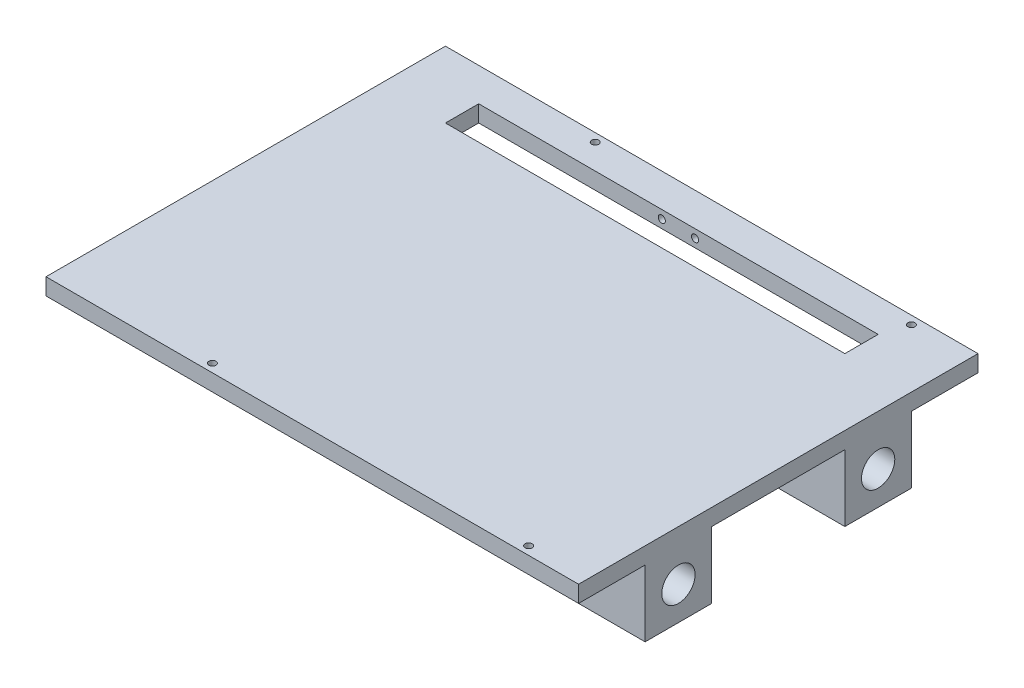
SolidWorks part; units mm, degrees
ref_plane "Front Plane" through (0, 0, 0) normal (0, 0, 1) x (1, 0, 0)
ref_plane "Top Plane" through (0, 0, 0) normal (0, 1, 0) x (1, 0, 0)
ref_plane "Right Plane" through (0, 0, 0) normal (1, 0, 0) x (0, 0, -1)
sketch "Sketch2" plane through (0, 0, 0) normal (0, 1, 0) x (1, 0, 0)
  line L1 (-101.6, -76.2) -> (101.6, -76.2)
  line L2 (-101.6, -76.2) -> (-101.6, 76.2)
  line L3 (-101.6, 76.2) -> (101.6, 76.2)
  line L4 (101.6, -76.2) -> (101.6, 76.2)
  line L5 (-101.6, -76.2) -> (101.6, 76.2) construction
  line L6 (-101.6, 76.2) -> (101.6, -76.2) construction
  point P0 (0, 0)
  dimension "D1" = 203.2
  dimension "D2" = 152.4
extrude "Boss-Extrude1" add sketch "Sketch2" along normal blind 6.35
sketch "Sketch3" plane through (0, 6.35, 0) normal (0, 1, 0) x (1, 0, 0)
  line L0 (-101.6, 0) -> (101.6, 0) construction
  line L1 (-101.6, 76.2) -> (-101.6, -76.2) construction
  line L2 (101.6, -76.2) -> (101.6, 76.2) construction
  line L3 (0, 76.2) -> (0, -76.2) construction
  line L4 (101.6, 76.2) -> (-101.6, 76.2) construction
  line L5 (-101.6, -76.2) -> (101.6, -76.2) construction
  line L7 (-76.2, 63.5) -> (76.2, 63.5)
  line L8 (-76.2, 63.5) -> (-76.2, 50.8)
  line L9 (-76.2, 50.8) -> (76.2, 50.8)
  line L10 (76.2, 63.5) -> (76.2, 50.8)
  line L11 (-76.2, 63.5) -> (76.2, 50.8) construction
  line L12 (-76.2, 50.8) -> (76.2, 63.5) construction
  point P12 (0, 57.15)
  dimension "D1" = 12.7
  dimension "D2" = 152.4
  dimension "D3" = 12.7
extrude "Cut-Extrude1" cut sketch "Sketch3" against normal blind 6.35
sketch "Sketch4" plane through (0, 0, 0) normal (0, -1, 0) x (1, 0, 0)
  line L0 (-101.6, -76.2) -> (-101.6, 76.2) construction
  line L1 (-101.6, 50.8) -> (-50.8, 50.8)
  line L2 (-101.6, 50.8) -> (-101.6, 25.4)
  line L3 (-101.6, 25.4) -> (-50.8, 25.4)
  line L4 (-50.8, 50.8) -> (-50.8, 25.4)
  line L5 (0, 76.2) -> (0, -76.2) construction
  line L6 (-101.6, 76.2) -> (101.6, 76.2) construction
  line L7 (101.6, -76.2) -> (-101.6, -76.2) construction
  line L8 (-101.6, 0) -> (101.6, 0) construction
  line L9 (101.6, 76.2) -> (101.6, -76.2) construction
  line L10 (101.6, 25.4) -> (50.8, 25.4)
  line L11 (50.8, 50.8) -> (50.8, 25.4)
  line L12 (101.6, 50.8) -> (50.8, 50.8)
  line L13 (101.6, 50.8) -> (101.6, 25.4)
  line L14 (101.6, -50.8) -> (101.6, -25.4)
  line L15 (101.6, -50.8) -> (50.8, -50.8)
  line L16 (50.8, -50.8) -> (50.8, -25.4)
  line L17 (101.6, -25.4) -> (50.8, -25.4)
  line L18 (-101.6, -25.4) -> (-50.8, -25.4)
  line L19 (-50.8, -50.8) -> (-50.8, -25.4)
  line L20 (-101.6, -50.8) -> (-50.8, -50.8)
  line L21 (-101.6, -50.8) -> (-101.6, -25.4)
  dimension "D1" = 25.4
  dimension "D2" = 50.8
  dimension "D3" = 25.4
sketch "Sketch6" plane through (0, 0, 0) normal (0, -1, 0) x (1, 0, 0)
  line L0 (0, -50.8) -> (0, -63.5) construction
  line L1 (-76.2, -50.8) -> (76.2, -50.8) construction
  line L2 (76.2, -63.5) -> (-76.2, -63.5) construction
extrude "Boss-Extrude2" add sketch "Sketch4" along normal blind 25.4
sketch "Sketch7" plane through (-101.6, 0, 0) normal (-1, 0, 0) x (0, 0, 1)
  line L0 (-38.1, -25.4) -> (-38.1, 6.35) construction
  line L1 (-25.4, -25.4) -> (-50.8, -25.4) construction
  line L2 (-76.2, 6.35) -> (76.2, 6.35) construction
  line L3 (-50.8, -12.7) -> (-25.4, -12.7) construction
  line L4 (-50.8, -25.4) -> (-50.8, 0) construction
  line L5 (-25.4, -25.4) -> (-25.4, 0) construction
  line L6 (38.1, -25.4) -> (38.1, 6.35) construction
  line L7 (50.8, -25.4) -> (25.4, -25.4) construction
  line L8 (25.4, -12.7) -> (50.8, -12.7) construction
  line L9 (25.4, -25.4) -> (25.4, 0) construction
  line L10 (50.8, -25.4) -> (50.8, 0) construction
  circle A0 centre (-38.1, -12.7) radius 6.35
  circle A1 centre (38.1, -12.7) radius 6.35
  dimension "D1" = 12.7
  dimension "D2" = 12.7
extrude "Cut-Extrude2" cut sketch "Sketch7" against normal blind 50.8
sketch "Sketch8" plane through (101.6, 0, 0) normal (1, 0, 0) x (0, 0, -1)
  line L0 (-50.8, -12.7) -> (50.8, -12.7) construction
  line L1 (-50.8, -25.4) -> (-50.8, 0) construction
  line L2 (50.8, -25.4) -> (50.8, 0) construction
  line L3 (-38.1, -25.4) -> (-38.1, 6.35) construction
  line L4 (50.8, -25.4) -> (25.4, -25.4) construction
  line L5 (38.1, -25.4) -> (38.1, 6.35) construction
  line L6 (-76.2, 6.35) -> (76.2, 6.35) construction
  line L7 (-25.4, -25.4) -> (-50.8, -25.4) construction
  circle A0 centre (-38.1, -12.7) radius 6.35
  circle A1 centre (38.1, -12.7) radius 6.35
  dimension "D1" = 12.7
  dimension "D2" = 12.7
extrude "Cut-Extrude3" cut sketch "Sketch8" against normal blind 50.8
ref_plane "Plane1" through (0, 0, 0) normal (-1, 0, 0) x (0, 0, 1)
ref_point "Point1"
sketch "Sketch12" plane through (0, 6.35, 0) normal (0, 1, 0) x (1, 0, 0)
  line L0 (101.6, 76.2) -> (-101.6, 76.2) construction
  line L1 (-38.1204, 76.2) -> (25.3796, 76.2)
  line L2 (-38.1204, 76.2) -> (-38.1204, 63.5)
  line L3 (-38.1204, 63.5) -> (25.3796, 63.5)
  line L4 (25.3796, 76.2) -> (25.3796, 63.5)
  line L5 (76.2, 63.5) -> (-76.2, 63.5) construction
  dimension "D1" = 63.5
hole_wizard "#6-32 Tapped Hole1" positions "Sketch13" profile "Sketch14" tap size "#6-32" standard "ANSI Inch"
sketch "Sketch13" plane through (0, 6.35, 0) normal (0, 1, 0) x (1, 0, 0)
  point P12 (-41.275, -73.025)
  point P15 (-41.275, 73.025)
  point P18 (79.375, 73.025)
  point P21 (79.375, -73.025)
cosmetic thread "Hole Thread6" parameters "D1"=11.43, "D2"=3.5052
cosmetic thread "Hole Thread7" parameters "D1"=11.43, "D2"=3.5052
cosmetic thread "Hole Thread8" parameters "D1"=11.43, "D2"=3.5052
cosmetic thread "Hole Thread9" parameters "D1"=11.43, "D2"=3.5052
sketch "Sketch14" plane through (-41.275, 6.35, 73.025) normal (1, 0, 0) x (0, 0, 1)
  line L0 (0, 0) -> (0, 13.5127)
  line L1 (0, 13.5127) -> (1.3525, 12.7)
  line L2 (1.3525, 12.7) -> (1.3525, 0)
  line L5 (1.3525, 0) -> (0, 0)
  line L10 (0, 13.5127) -> (-1.3526, 12.7) construction
  line L11 (0, -6.35) -> (0, 107.95) construction
  dimension "Tap Drill Dia." = 2.7051
  dimension "Tap Drill Depth" = 12.7
  dimension "Drill Angle" = 118
hole_wizard "#6-32 Tapped Hole2" positions "Sketch18" profile "Sketch19" tap size "#6-32" standard "ANSI Inch" end condition up to next
sketch "Sketch18" plane through (0, 0, -76.2) normal (0, 0, -1) x (-1, 0, 0)
  line L0 (38.1204, 6.35) -> (-25.3796, 6.35) construction
  line L1 (101.6, 6.35) -> (101.6, 0) construction
  point P0 (-6.35, 3.175)
  point P2 (6.35, 3.175)
  dimension "D1" = 12.7
  dimension "D2" = 3.175
  dimension "D3" = 95.25
sketch "Sketch19" plane through (6.35, 3.175, -76.2) normal (1, 0, 0) x (0, 1, 0)
  line L0 (0, 0) -> (0, 12.7)
  line L1 (0, 12.7) -> (1.3525, 12.7)
  line L2 (1.3525, 12.7) -> (1.3525, 0)
  line L5 (1.3525, 0) -> (0, 0)
  line L11 (0, -6.35) -> (0, 107.95) construction
  dimension "Thru Tap Drill Dia." = 2.7051
  dimension "Thru Tap Drill Depth" = 12.7
cosmetic thread "Hole Thread10" parameters "D2"=3.5052
cosmetic thread "Hole Thread11" parameters "D2"=3.5052
